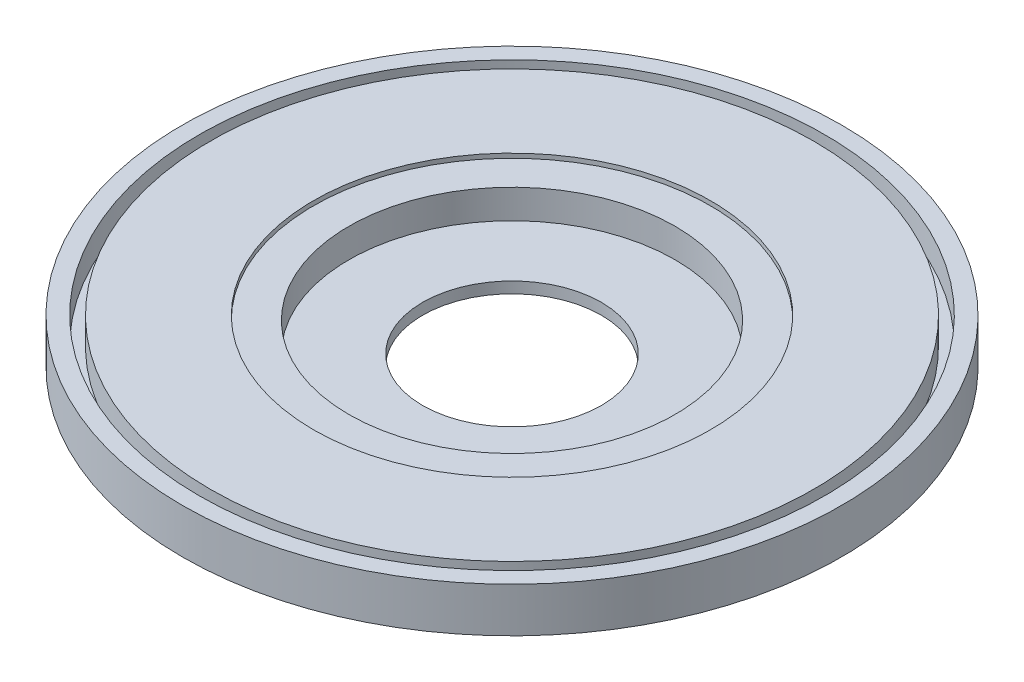
SolidWorks part; units mm, degrees
material "6061-T6 (SS)"
ref_plane "Front Plane" through (0, 0, 0) normal (0, 0, 1) x (1, 0, 0)
ref_plane "Top Plane" through (0, 0, 0) normal (0, 1, 0) x (1, 0, 0)
ref_plane "Right Plane" through (0, 0, 0) normal (1, 0, 0) x (0, 0, -1)
sketch "Sketch1" plane through (0, 0, 0) normal (0, 1, 0) x (1, 0, 0)
  line L5 (0, 0) -> (127.635, 0)
  line L6 (0, 0) -> (0, 127.635)
  line L7 (0, 127.635) -> (127.635, 127.635)
  line L8 (127.635, 0) -> (127.635, 127.635)
  dimension "D1" = 127.635
  dimension "D2" = 127.635
extrude "Boss-Extrude1" add sketch "Sketch1" along normal blind 9.525 contours L5 L8 L7 L6
sketch "Sketch13" plane through (0, 9.525, 0) normal (0, 1, 0) x (1, 0, 0)
  circle A0 centre (63.8175, 63.8175) radius 93.6625
  dimension "D1" = 187.325
extrude "Boss-Extrude2" add sketch "Sketch13" against normal blind 12.7 contours A0
sketch "Sketch6" [suppressed] plane through (127.635, 0, 0) normal (1, 0, 0) x (0, 0, -1)
  circle A0 centre (4.7625, 4.7625) radius 1.3526
  dimension "D1" = 2.7051
extrude "6-32 hole1" [suppressed] cut sketch "Sketch6" against normal blind 12.7
sketch "Sketch7" [suppressed] plane through (0, 0, -127.635) normal (0, 0, -1) x (-1, 0, 0)
  circle A0 centre (-122.8725, 4.7625) radius 1.3525
  dimension "D1" = 2.7051
sketch "Sketch8" [suppressed] plane through (0, 0, 0) normal (-1, 0, 0) x (0, 0, 1)
  circle A0 centre (-122.8725, 4.7625) radius 1.3525
  dimension "D1" = 2.7051
sketch "Sketch9" [suppressed] plane through (0, 0, 0) normal (0, 0, 1) x (1, 0, 0)
  circle A0 centre (4.7625, 4.7625) radius 1.3526
  dimension "D1" = 2.7051
sketch "Sketch5" plane through (0, 9.525, 0) normal (0, 1, 0) x (1, 0, 0)
  circle A0 centre (63.8175, 63.8175) radius 46.355
  circle A1 centre (63.8175, 63.8175) radius 93.6625 construction
  dimension "D1" = 92.71
extrude "Cut-Extrude1" cut sketch "Sketch5" against normal blind 9.525
sketch "Sketch11" plane through (0, 9.525, 0) normal (0, 1, 0) x (1, 0, 0)
  line L0 (63.8175, 63.8175) -> (63.8175, 115.443) construction
  circle A0 centre (63.8175, 115.443) radius 1.4351
  dimension "D2" = 2.8702
  dimension "D1" = 51.6255
extrude "Cut-Extrude3" [suppressed] cut sketch "Sketch11" against normal through all contours A0
pattern_circular "CirPattern1" [suppressed] count 12 over 360 of bodies 108
sketch "Sketch12" plane through (0, 9.525, 0) normal (0, 1, 0) x (1, 0, 0)
  circle A0 centre (63.8175, 63.8175) radius 56.4198
  dimension "D1" = 112.8395
extrude "Cut-Extrude4" cut sketch "Sketch12" against normal blind 1.27
sketch "Sketch15" plane through (0, 9.525, 0) normal (0, 1, 0) x (1, 0, 0)
  line L0 (63.8175, 63.8175) -> (-29.845, 63.8175) construction
  line L1 (0, -39.1057) -> (0, 39.1057) construction
  line L2 (-20.0025, 63.8175) -> (-25.0825, 63.8175)
  line L3 (-8.7458, 105.7742) -> (-13.2051, 108.2104)
  line L4 (-8.7458, 105.7742) -> (-20.0025, 63.8175) construction
  circle A0 centre (63.8175, 63.8175) radius 56.4198 construction
  arc A1 (-20.0025, 63.8175) -> (-8.7458, 105.7742) centre (63.8175, 63.8175) cw
  arc A2 (-25.0825, 63.8175) -> (-13.2051, 108.2104) centre (63.8175, 63.8175) cw
  circle A3 centre (63.8175, 63.8175) radius 93.6625 construction
  point P0 (63.8175, 63.8175)
  point P11 (-14.3741, 84.7959)
  dimension "D1" = 46.482
  dimension "D2" = 88.9
  dimension "D3" = 83.82
  dimension "D4" = 43.942
sketch "Sketch16" plane through (0, 9.525, 0) normal (0, 1, 0) x (1, 0, 0)
  circle A0 centre (63.8175, 63.8175) radius 88.9
  circle A1 centre (63.8175, 63.8175) radius 85.725
  dimension "D1" = 177.8
  dimension "D2" = 171.45
extrude "Cut-Extrude5" cut sketch "Sketch16" against normal blind 7.62
sketch "Sketch18" plane through (0, 8.255, 0) normal (0, 1, 0) x (1, 0, 0)
  line L0 (63.8175, 185.7252) -> (63.8175, -48.6103) construction
ref_plane "Plane1" through (63.8175, 0, 0) normal (-1, 0, 0) x (0, 0, 1)
ref_plane "Plane2" through (0, 0, 29.845) normal (0, 0, 1) x (1, 0, 0)
sketch "Sketch17" plane through (0, 0, 29.845) normal (0, 0, 1) x (1, 0, 0)
  line L0 (63.8175, 103.0287) -> (63.8175, -103.0287) construction
  line L1 (157.48, 9.525) -> (-29.845, 9.525) construction
  circle A0 centre (63.8175, 5.715) radius 1.4351
  dimension "D1" = 2.8702
  dimension "D2" = 3.81
extrude "Cut-Extrude6" [suppressed] cut sketch "Sketch17" against normal blind 15.24
pattern_circular "CirPattern2" [suppressed] count 12 over 360 reverse direction yes of bodies 116
sketch "Sketch19" plane through (0, -3.175, 0) normal (0, -1, 0) x (1, 0, 0)
  circle A0 centre (63.8175, -63.8175) radius 25.4
  dimension "D1" = 50.8
extrude "Cut-Extrude7" cut sketch "Sketch19" against normal blind 87.63
